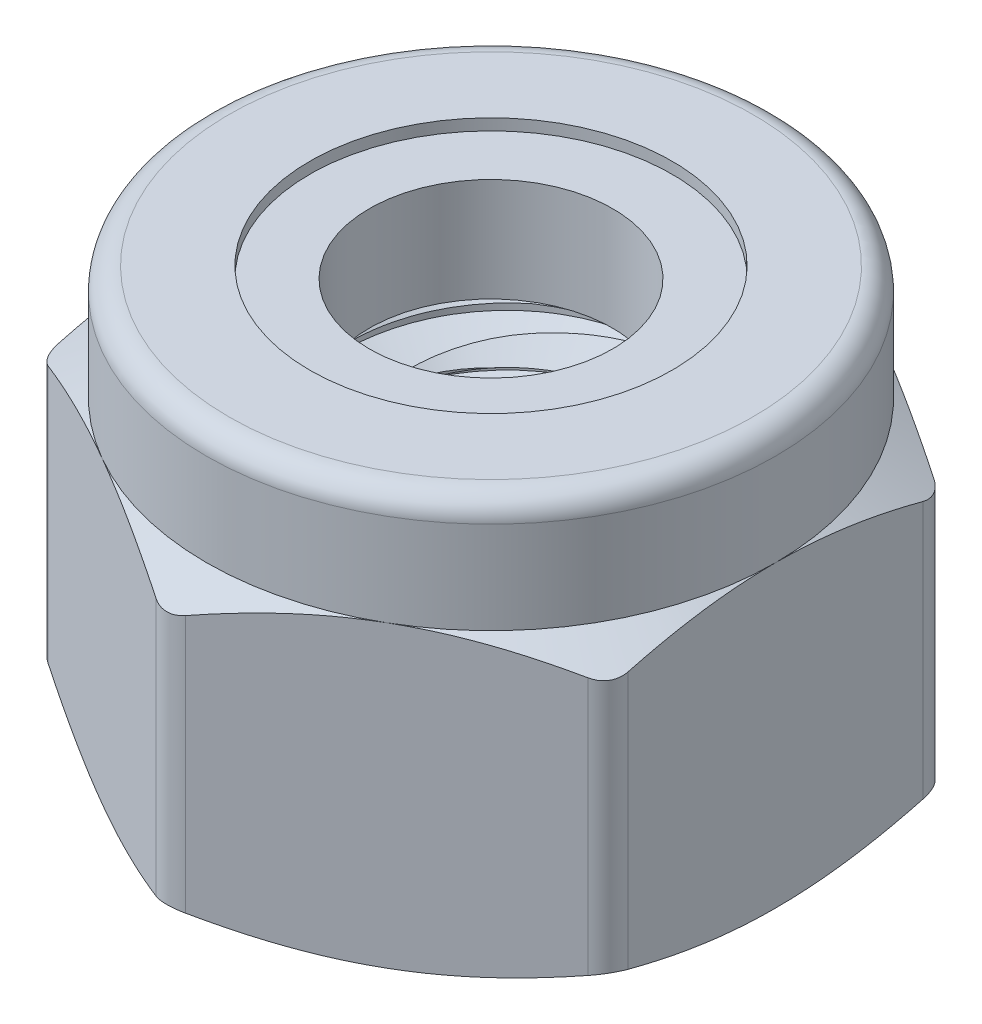
SolidWorks part; units mm, degrees
ref_plane "Front Plane" through (0, 0, 0) normal (0, 0, 1) x (1, 0, 0)
ref_plane "Top Plane" through (0, 0, 0) normal (0, 1, 0) x (1, 0, 0)
ref_plane "Right Plane" through (0, 0, 0) normal (1, 0, 0) x (0, 0, -1)
sketch "Sketch1" plane through (0, 0, 0) normal (0, 0, 1) x (1, 0, 0)
  line L0 (-2.75, -2) -> (2.75, -2) construction
  line L1 (-2.75, -2) -> (-2.75, 0.8904) construction
  line L2 (-2.75, 0.8904) -> (2.75, 0.8904) construction
  line L7 (2.75, 0.8904) -> (2.75, -2) construction
  line L8 (0, 2) -> (0, -2) construction
  line L9 (-1.5, 2) -> (-1.5, -2) construction
  line L10 (1.5, 2) -> (1.5, -2) construction
  line L11 (-1.5, 2) -> (1.5, 2) construction
  line L14 (2.75, -2) -> (3.1747, -1.7548) construction
  line L15 (2.75, 0.8904) -> (2.75, 2) construction
  line L16 (2.75, 2) -> (1.5, 2) construction
  line L17 (3.1747, -1.7548) -> (3.1747, 0.6452) construction
  line L18 (-2.75, 0.8904) -> (-2.75, 2) construction
  line L19 (-2.75, 2) -> (-1.5, 2) construction
  line L20 (3.1747, 0.6452) -> (2.75, 0.8904) construction
  line L21 (-1.5, -2) -> (-1.5, -2.4375) construction
  line L22 (-1.5, -2.4375) -> (-1.1211, -2.2188) construction
  line L23 (-1.1211, -2.2188) -> (-1.5, -2) construction
  line L24 (-1.5541, -1.9688) -> (-1.5541, -2.4688) construction
  line L25 (-1.5541, -1.9688) -> (-1.5, -2) construction
  line L26 (-1.5, -2.4375) -> (-1.5541, -2.4688) construction
  line L27 (-1.1752, -2.1875) -> (-1.1752, -2.25) construction
  line L28 (-1.5, -2.2188) -> (-1.5541, -2.2188) construction
  line L29 (-1.1752, -2.2188) -> (-1.1211, -2.2188) construction
  dimension "Width | s" = 5.5
  dimension "Thread Diameter" = 3
  dimension "Height | h" = 4
  dimension "D1" = 6.3494
  dimension "D2" = 30
  dimension "Flats Height" = 2.4
  dimension "Thread Pitch" = 0.5
  dimension "D4" = 0.0625
sketch "Sketch2" plane through (0, 0, 0) normal (0, 1, 0) x (1, 0, 0)
  line L0 (0, 0) -> (1.375, 2.3816) construction
  line L1 (2.75, 1.5877) -> (0, 3.1754)
  line L2 (0, 3.1754) -> (-2.75, 1.5877)
  line L3 (-2.75, 1.5877) -> (-2.75, -1.5877)
  line L4 (-2.75, -1.5877) -> (0, -3.1754)
  line L5 (0, -3.1754) -> (2.75, -1.5877)
  line L6 (2.75, -1.5877) -> (2.75, 1.5877)
  line L7 (0, 0) -> (2.75, 1.5877) construction
  circle A0 centre (0, 0) radius 2.75 construction
  circle A1 centre (0, 0) radius 3.1754 construction
extrude "Boss-Extrude1" add sketch "Sketch2" against normal up to vertex (2 mm away) from vertex up to point (2.75, -2, 0) starting at point (2.75, 0.8904, 0)
sketch "Sketch3" plane through (0, 0, 0) normal (0, 0, 1) x (1, 0, 0)
  line L3 (1.5, 1.6121) -> (3.1847, 0.6394)
  line L4 (1.5, 2) -> (1.5, -2) construction
  line L5 (1.5, -2.7217) -> (3.1847, -1.749)
  line L6 (3.1847, -1.749) -> (3.1847, -2.7217)
  line L7 (3.1847, -2.7217) -> (1.5, -2.7217)
  line L8 (1.5, 1.6121) -> (3.1847, 1.6121)
  line L10 (3.1847, 0.6394) -> (3.1847, 1.6121)
  dimension "D1" = 0.01
revolve "Cut-Revolve1" cut sketch "Sketch3" angle 360 about L8
fillet "Fillet1" radius 0.2831 6 edges at (-2.75, -0.5548, -1.5877) (-2.75, -0.5548, 1.5877) (0, -0.5548, 3.1754) (0, -0.5548, -3.1754) (2.75, -0.5548, -1.5877) (2.75, -0.5548, 1.5877)
sketch "Sketch5" plane through (0, 0, 0) normal (0, 0, 1) x (1, 0, 0)
  line L0 (-1.75, -2) -> (-1.5, -1.75)
  line L1 (-2.75, -2) -> (2.75, -2) construction
  line L2 (-1.5, 2) -> (-1.5, -2) construction
  line L3 (-1.5, -1.75) -> (-1.5, 0.6404)
  line L4 (-1.5, 0.6404) -> (-1.75, 0.8904)
  line L5 (-2.75, 0.8904) -> (2.75, 0.8904) construction
  line L6 (-1.75, 0.8904) -> (0, 0.8904)
  line L7 (0, 0.8904) -> (0, -2)
  line L8 (0, -2) -> (-1.75, -2)
  line L9 (0, 2) -> (0, -2) construction
  dimension "D1" = 45
  dimension "D2" = 0.25
revolve "Cut-Revolve2" cut sketch "Sketch5" angle 360 about L8
sketch "Sketch4" plane through (0, 0, 0) normal (0, 0, 1) x (1, 0, 0)
  line L0 (-1.75, 2) -> (-2.5313, 2)
  line L1 (-2.75, 2) -> (-1.5, 2) construction
  line L2 (-2.75, 1.7813) -> (-2.75, 0.8904)
  line L4 (-2.5313, 2) -> (-2.5313, 1.7813) construction
  line L5 (-1.3106, -2.1094) -> (-1.3106, -2.3281) construction
  line L6 (-1.1211, -2.2188) -> (-1.5, -2) construction
  line L7 (-1.5, -2.4375) -> (-1.1211, -2.2188) construction
  line L8 (-2.75, 0.8904) -> (-2.6406, 0.8904)
  line L10 (-1.75, 1.8906) -> (-1.75, 2)
  line L11 (-1.75, 1.8906) -> (-2.5313, 1.8906)
  line L12 (-2.6406, 1.7813) -> (-2.6406, 0.8904)
  arc A0 (-2.75, 1.7813) -> (-2.5313, 2) centre (-2.5313, 1.7813) cw
  arc A1 (-2.5313, 1.8906) -> (-2.6406, 1.7813) centre (-2.5313, 1.7813) ccw
revolve "Revolve1" add sketch "Sketch4" angle 360 about L8
sketch "Sketch6" plane through (0, 0, 0) normal (0, 0, 1) x (1, 0, 0)
  line L0 (-2.75, 0.8904) -> (2.75, 0.8904) construction
  line L1 (-2.5313, 1.8906) -> (-1.1752, 1.8906)
  line L2 (-2.6406, 1.7813) -> (-2.6406, 0.8904)
  line L3 (-2.6406, 0.8904) -> (-1.1752, 0.8904)
  line L4 (-1.1752, 1.8906) -> (-1.1752, 0.8904)
  arc A0 (-2.5313, 1.8906) -> (-2.6406, 1.7813) centre (-2.5313, 1.7813) ccw
revolve "Revolve2" add sketch "Sketch6" angle 360 about L8
sketch "Sketch7" plane through (0, -2, 0) normal (0, 1, 0) x (-1, 0, 0)
  line L0 (1.5, 0) -> (-1.5, 0) construction
  line L1 (0, 0) -> (-1.0607, -1.0607) construction
  circle A0 centre (0, 0) radius 1.5
  point P7 (-1.0607, -1.0607)
  dimension "D1" = 225
curve "Helix/Spiral1" pitch 0.5 height 4 radius 1.5 left hand yes centre (0, -2, 0) axis (0, 1, 0) start towards (0, 0, 1)
sketch "Sketch8" plane through (0, 0, 0) normal (0, 0, 1) x (1, 0, 0)
  line L0 (-1.5271, -1.9844) -> (-1.5271, -2.4531)
  line L1 (-1.5541, -1.9688) -> (-1.5, -2) construction
  line L2 (-1.5, -2.4375) -> (-1.5541, -2.4688) construction
  line L3 (-1.5271, -2.4531) -> (-1.1752, -2.25)
  line L4 (-1.1752, -2.25) -> (-1.1752, -2.1875)
  line L5 (-1.1752, -2.1875) -> (-1.5271, -1.9844)
sweep "Sweep1" add profiles "Sketch8" path "Helix/Spiral1"
sketch "Sketch9" plane through (0, 0, 0) normal (0, 0, 1) x (1, 0, 0)
  line L0 (-1.75, 2.1094) -> (-1.75, 0.8904)
  line L1 (-1.75, 0.8904) -> (-1.1211, 0.2615)
  line L2 (-1.1211, 0.2615) -> (-1.1211, 2.1094)
  line L4 (-1.1211, 2.1094) -> (-1.75, 2.1094)
  line L5 (-1.1211, -1.3711) -> (-1.75, -2)
  line L6 (-1.75, -2) -> (-1.75, -2.4688)
  line L7 (-1.75, -2.4688) -> (-1.1211, -2.4688)
  line L8 (-1.1211, -2.4688) -> (-1.1211, -1.3711)
  line L9 (-1.4356, 2.1094) -> (-1.4356, 2) construction
  line L10 (-1.5, 2) -> (1.5, 2) construction
  line L12 (-1.75, 1.8906) -> (-1.75, 2) construction
revolve "Cut-Revolve3" cut sketch "Sketch9" angle 360 about L8
equation "\"D1@Sketch1\"=\"Width | s@Sketch1\"*(1.15+.04/9)"
equation "\"D1@Fillet1\"=(\"D1@Sketch1\"-\"Width | s@Sketch1\")/3"
equation "\"D4@Sketch1\" = \"Thread Pitch@Sketch1\" / 8"
equation "\"D2@Sketch5\"=\"Thread Pitch@Sketch1\"*.5"
equation "\"D3@Helix/Spiral1\"=\"Height | h@Sketch1\""
equation "\"D4@Helix/Spiral1\"=\"Thread Pitch@Sketch1\""
